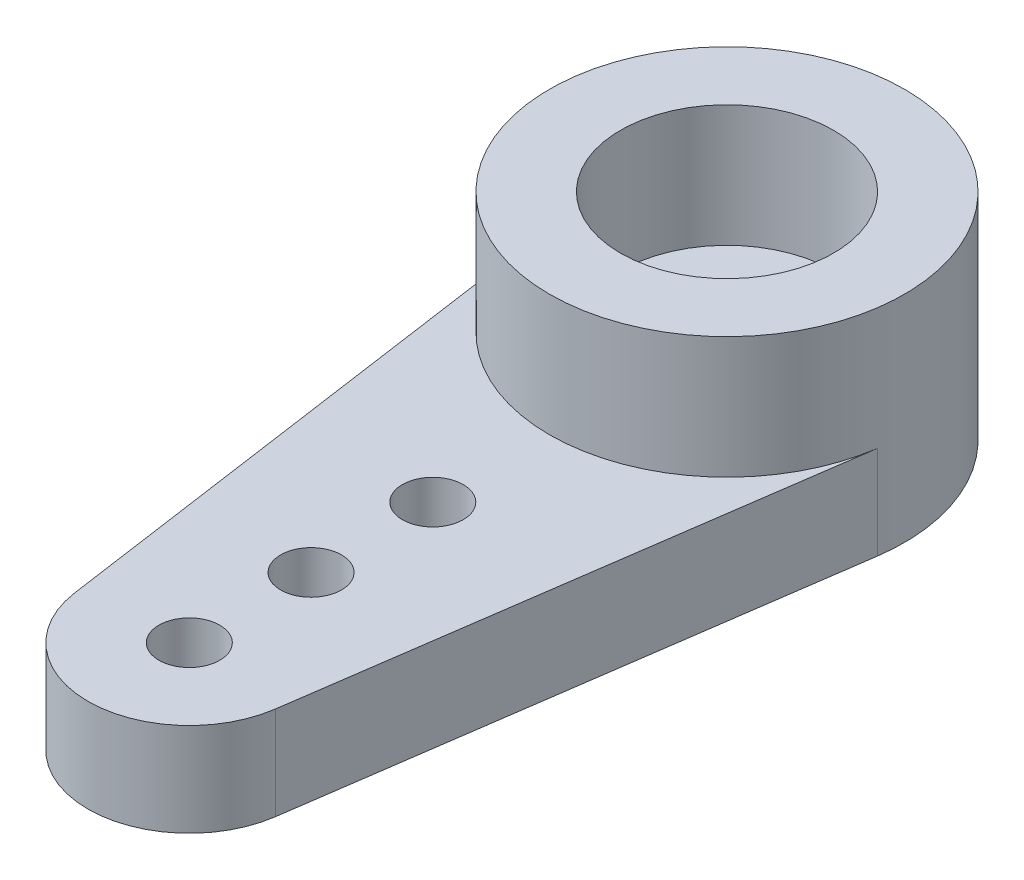
SolidWorks part; units mm, degrees
ref_plane "Front Plane" through (0, 0, 0) normal (0, 0, 1) x (1, 0, 0)
ref_plane "Top Plane" through (0, 0, 0) normal (0, 1, 0) x (1, 0, 0)
ref_plane "Right Plane" through (0, 0, 0) normal (1, 0, 0) x (0, 0, -1)
sketch "Sketch1" plane through (0, 0, 0) normal (0, 1, 0) x (1, 0, 0)
  circle A0 centre (0, 0) radius 4.375
  circle A1 centre (0, 0) radius 2.625
  dimension "D1" = 8.75
  dimension "D2" = 5.25
extrude "Boss-Extrude1" add sketch "Sketch1" along normal blind 3
sketch "Sketch2" plane through (0, 0, 0) normal (0, -1, 0) x (1, 0, 0)
  line L0 (0, 0) -> (0, 13.25) construction
  line L1 (-2.4748, 13.6038) -> (-4.331, 0.6191)
  line L2 (2.4748, 13.6038) -> (4.331, 0.6191)
  arc A0 (-4.331, 0.6191) -> (4.331, 0.6191) centre (0, 0) ccw
  circle A1 centre (0, 0) radius 4.375 construction
  circle A2 centre (0, 0) radius 1.425
  circle A3 centre (0, 13.25) radius 0.75
  circle A5 centre (0, 10.25) radius 0.75
  circle A6 centre (0, 7.25) radius 0.75
  arc A7 (2.4748, 13.6038) -> (-2.4748, 13.6038) centre (0, 13.25) ccw
  dimension "D1" = 2.85
  dimension "D3" = 1.5
  dimension "D4" = 3
  dimension "D6" = 5
  dimension "D2" = 13.25
  dimension "D5" = 3
extrude "Boss-Extrude2" add sketch "Sketch2" along normal blind 2.3
